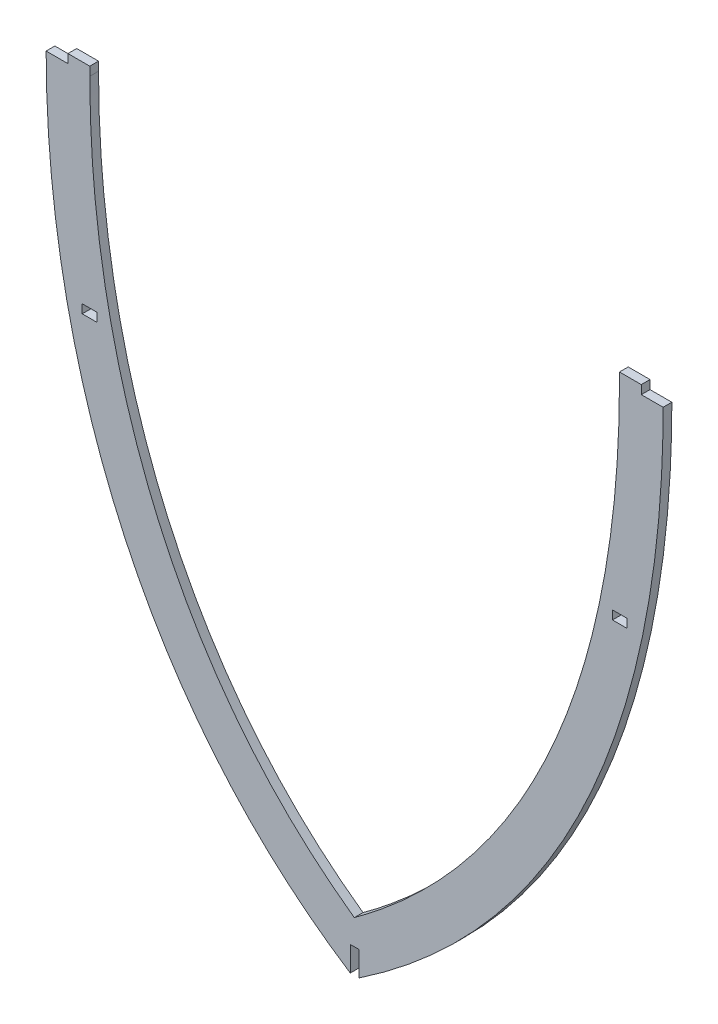
SolidWorks part; units mm, degrees
material "birch 3mm plywood"
ref_plane "Front" through (0, 0, 0) normal (0, 0, 1) x (1, 0, 0)
ref_plane "Top" through (0, 0, 0) normal (0, 1, 0) x (1, 0, 0)
ref_plane "Right" through (0, 0, 0) normal (1, 0, 0) x (0, 0, -1)
sketch "Sketch1" plane through (0, 0, 0) normal (0, 0, 1) x (1, 0, 0)
  line L0 (-88.6, -152) -> (-93.6, -152) construction
  line L1 (-93.6, -152) -> (-93.6, -155) construction
  line L2 (-93.6, -155) -> (-88.6, -155) construction
  line L3 (-88.6, -155) -> (-88.6, -152) construction
  line L4 (93.6, -152) -> (88.6, -152) construction
  line L5 (88.6, -152) -> (88.6, -155) construction
  line L6 (88.6, -155) -> (93.6, -155) construction
  line L7 (93.6, -155) -> (93.6, -152) construction
  line L8 (-88.6, -152) -> (-93.6, -152)
  line L9 (-93.6, -152) -> (-93.6, -155)
  line L10 (-93.6, -155) -> (-88.6, -155)
  line L11 (-88.6, -155) -> (-88.6, -152)
  line L12 (93.6, -152) -> (88.6, -152)
  line L13 (88.6, -152) -> (88.6, -155)
  line L14 (88.6, -155) -> (93.6, -155)
  line L15 (93.6, -155) -> (93.6, -152)
  line L16 (-106, -83) -> (-98.5, -83)
  line L17 (-106, -83) -> (-68.5834, -83) construction
  line L18 (-98.5, -83) -> (-98.5, -80)
  line L19 (-68.5834, -80) -> (-106, -80) construction
  line L20 (-98.5, -80) -> (-91, -80)
  line L21 (-91, -80) -> (-91, -83)
  line L22 (106, -83) -> (98.5, -83)
  line L23 (68.5834, -83) -> (106, -83) construction
  line L24 (98.5, -83) -> (98.5, -80)
  line L25 (106, -80) -> (68.5834, -80) construction
  line L26 (98.5, -80) -> (91, -80)
  line L27 (91, -80) -> (91, -83)
  spline S0 degree 3 poles (-686.265, -1689.3768) (-927.6562, 3138.3549) (1865.5231, -2297.897) (-1800.5014, 488.8359) knots -5.474835 -5.474835 -5.474835 -5.474835 3.700943 3.700943 3.700943 3.700943 only from (106, -83) to (0, -306.0893) construction
  spline S1 degree 3 poles (640.9937, -1850.1248) (295.6073, 2811.9474) (-1313.8302, -2440.4005) (1644.8902, 765.8753) knots -4.232502 -4.232502 -4.232502 -4.232502 3.567732 3.567732 3.567732 3.567732 only from (-106, -83) to (0, -306.0893) construction
  spline S2 degree 3 poles (106, -83) (106, -174.4433) (74.7629, -256.783) (0, -306.0893) knots 0 0 0 0 1 1 1 1
  spline S3 degree 3 poles (-106, -83) (-106, -171.1717) (-74.7629, -258.4392) (0, -306.0893) knots 0 0 0 0 1 1 1 1
  spline S4 degree 1 poles (-91, -83) (-0.1167, -287.9264) knots 0 0 1 1 construction
  spline S5 degree 1 poles (91, -83) (-0.1167, -287.9264) knots 0 0 1 1 construction
  spline S6 degree 3 poles (-91, -83) (-91, -88.0686) (-90.7842, -98.2205) (-89.4717, -118.3778) (-86.1468, -143.2308) (-79.3681, -172.0711) (-69.7174, -199.532) (-57.1183, -225.2317) (-44.0961, -244.8889) (-32.112, -259.4019) (-22.3248, -269.6427) (-13.4811, -277.6134) (-5.9927, -283.6258) (-2.0894, -286.5211) (-0.1167, -287.9264) knots 0 0 0 0 0.059983 0.119967 0.239934 0.359901 0.479868 0.599835 0.719802 0.779785 0.839769 0.899752 0.929744 0.959735 0.959735 0.959735 0.959735
  spline S7 degree 3 poles (-0.1167, -287.9264) (1.8708, -286.4802) (5.8114, -283.5064) (13.356, -277.3846) (22.2576, -269.3453) (32.0901, -259.1217) (44.1097, -244.7411) (57.1396, -225.4116) (69.7252, -200.2046) (79.363, -173.1605) (85.0093, -149.2619) (88.136, -129.4393) (89.7964, -114.2526) (90.6189, -101.351) (90.9458, -90.91) (91, -85.632) (91, -83) knots 0 0 0 0 0.030008 0.060016 0.120032 0.180048 0.240064 0.360096 0.480129 0.600161 0.720193 0.780209 0.840225 0.900241 0.930249 0.960257 0.960257 0.960257 0.960257
  dimension "D2" = 7.5
  dimension "D3" = 7.5
  dimension "D1" = 15
extrude "Boss-Extrude1" add sketch "Sketch1" along normal mid plane 3
sketch "Sketch2" plane through (0, 0, 1.5) normal (0, 0, 1) x (1, 0, 0)
  line L0 (-1.5, -296.5952) -> (1.5, -296.5952)
  line L1 (1.5, -296.5952) -> (1.5, -306.0893)
  line L2 (1.5, -306.0893) -> (-1.5, -306.0893)
  line L3 (1.5, -306.0893) -> (-1.5, -306.0893) construction
  line L4 (-1.5, -83) -> (-1.5, -306.0893) construction
  line L5 (-1.5, -306.0893) -> (-1.5, -296.5952)
extrude "Cut-Extrude1" cut sketch "Sketch2" against normal blind 3
